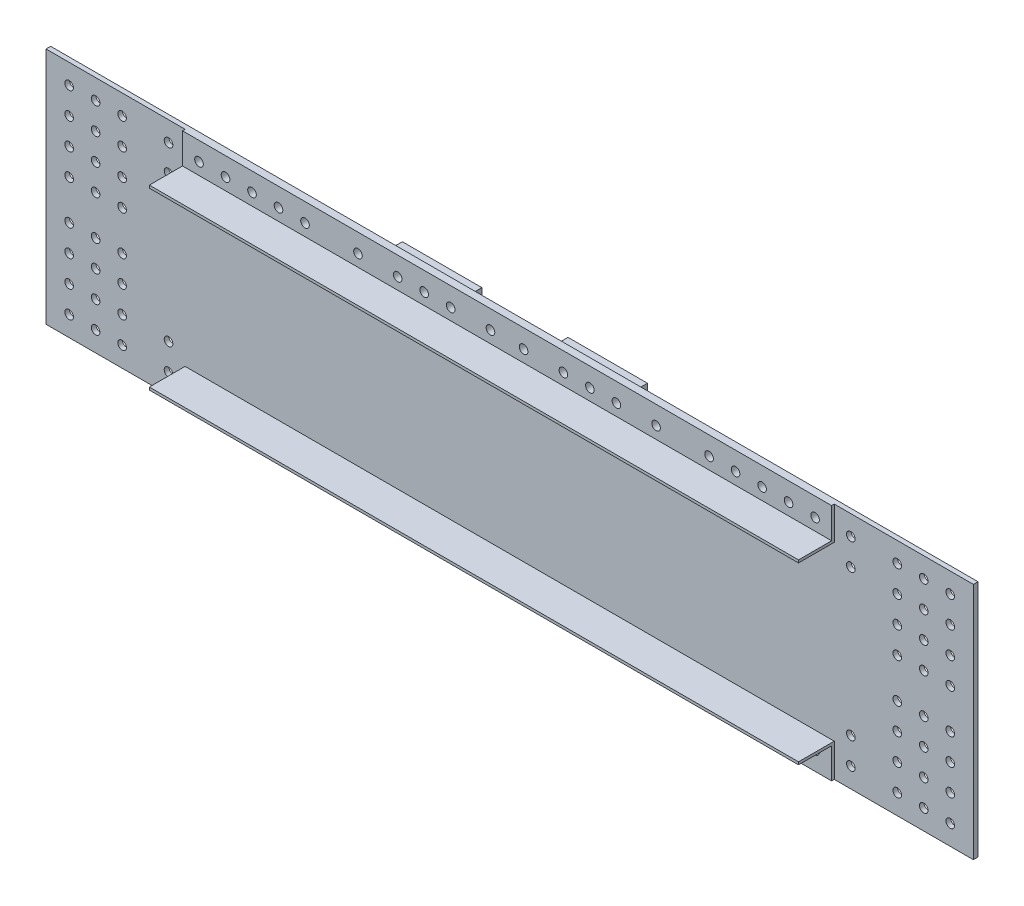
SolidWorks part; units mm, degrees
note: The reader was unsure of these and kept them because the rebuilt part matched: shared geometry of "草图11<3>".
ref_plane "前视基准面" through (0, 0, 0) normal (0, 0, 1) x (1, 0, 0)
ref_plane "上视基准面" through (0, 0, 0) normal (0, 1, 0) x (1, 0, 0)
ref_plane "右视基准面" through (0, 0, 0) normal (1, 0, 0) x (0, 0, -1)
sketch "草图1" plane through (0, 0, 0) normal (0, 0, 1) x (1, 0, 0)
  line L1 (-1400, 360) -> (1400, 360)
  line L2 (-1400, 360) -> (-1400, -360)
  line L3 (-1400, -360) -> (1400, -360)
  line L4 (1400, 360) -> (1400, -360)
  line L5 (-1400, 360) -> (1400, -360) construction
  line L6 (-1400, -360) -> (1400, 360) construction
  point P0 (0, 0)
extrude "凸台-拉伸1" add sketch "草图1" along normal blind 14
sketch "草图2" plane through (0, 0, 14) normal (0, 0, 1) x (1, 0, 0)
  line L0 (-1400, 300) -> (1400, 300)
  line L1 (-1400, 360) -> (-1400, -360) construction
  line L2 (1400, -360) -> (1400, 360) construction
  line L3 (1400, 360) -> (-1400, 360) construction
  line L4 (-1400, 304) -> (1400, 304)
  line L5 (-1330, 360) -> (-1330, -360)
  line L6 (-1400, -360) -> (1400, -360) construction
  line L7 (-1030, 360) -> (-1030, -360)
  line L8 (-980, 360) -> (-980, -360)
  dimension "D1" = 60
  dimension "D2" = 56
  dimension "D3" = 70
  dimension "D4" = 370
  dimension "D5" = 420
sketch "草图3" plane through (0, 0, 14) normal (0, 0, 1) x (1, 0, 0)
  circle A0 centre (-1330.2106, 299.6366) radius 13
extrude "切除-拉伸1" cut sketch "草图3" against normal through all
pattern_linear "阵列(线性)1" count 3 spacing 80 along (1, 0, 0) count 4 spacing 80 along (0, -1, 0) of "切除-拉伸1"
sketch "草图4" plane through (0, 0, 14) normal (0, 0, 1) x (1, 0, 0)
  circle A0 centre (-1030.0292, 300.0161) radius 13
extrude "切除-拉伸2" cut sketch "草图4" against normal through all
pattern_linear "阵列(线性)2" count 2 spacing 80 along (0, -1, 0) of "切除-拉伸2"
mirror "镜向1" about plane through (0, 0, 0) normal (0, 1, 0) of "阵列(线性)1", "阵列(线性)2", "切除-拉伸1", "切除-拉伸2"
mirror "镜向2" about plane through (0, 0, 0) normal (1, 0, 0) of "镜向1", "切除-拉伸1", "阵列(线性)1", "切除-拉伸2", "阵列(线性)2"
sketch "草图5" plane through (0, 0, 14) normal (0, 0, 1) x (1, 0, 0)
  line L1 (-980, 360) -> (0, 360)
  line L2 (-980, 360) -> (-980, 260)
  line L3 (-980, 260) -> (0, 260)
  line L4 (0, 360) -> (0, 260)
extrude "凸台-拉伸2" add sketch "草图5" along normal blind 8
sketch "草图6" plane through (0, 0, 14) normal (0, 0, 1) x (1, 0, 0)
  line L0 (-930, 360) -> (-930, -360)
  line L1 (0, 360) -> (-980, 360) construction
  line L2 (-1400, -360) -> (1400, -360) construction
  line L3 (-980, 360) -> (-980, -360) construction
  line L4 (-450, 360) -> (-450, -360)
  line L5 (-330, 360) -> (-330, -360)
  line L6 (-50, 360) -> (-50, -360)
  dimension "D1" = 50
  dimension "D2" = 530
  dimension "D3" = 650
  dimension "D4" = 930
sketch "草图7" plane through (0, 0, 22) normal (0, 0, 1) x (1, 0, 0)
  line L0 (-1400, 304) -> (1400, 304) construction
  line L1 (-930, 360) -> (-930, -360) construction
  circle A0 centre (-930, 304) radius 13
extrude "切除-拉伸3" cut sketch "草图7" against normal through all
pattern_linear "阵列(线性)3" count 5 spacing 80 along (1, 0, 0) of "切除-拉伸3"
sketch "草图8" plane through (0, 0, 22) normal (0, 0, 1) x (1, 0, 0)
  line L0 (-1400, 304) -> (1400, 304) construction
  line L1 (-450, 360) -> (-450, -360) construction
  line L2 (-50, 360) -> (-50, -360) construction
  circle A0 centre (-450, 304) radius 13
  circle A1 centre (-50, 304) radius 13
extrude "切除-拉伸4" cut sketch "草图8" against normal through all
sketch "草图9" plane through (0, 0, 22) normal (0, 0, 1) x (1, 0, 0)
  line L0 (0, 260) -> (0, 360) construction
  line L1 (-980, 260) -> (0, 260)
  line L2 (-980, 260) -> (-980, 268)
  line L3 (-980, 268) -> (0, 268)
  line L4 (0, 260) -> (0, 268)
extrude "凸台-拉伸3" add sketch "草图9" along normal blind 100
mirror "镜向3" about plane through (0, 0, 0) normal (0, 1, 0) of "凸台-拉伸2", "阵列(线性)3", "切除-拉伸4", "凸台-拉伸3", "切除-拉伸3"
mirror "镜向4" about plane through (0, 0, 0) normal (1, 0, 0) of "镜向3", "凸台-拉伸2", "切除-拉伸3", "阵列(线性)3", "切除-拉伸4"
sketch "草图10" plane through (0, 0, 0) normal (0, 0, -1) x (-1, 0, 0)
  line L0 (370, -360) -> (370, 360)
  line L1 (1400, -360) -> (-1400, -360) construction
  line L2 (-1400, 360) -> (1400, 360) construction
  line L3 (330, 360) -> (330, -360) construction
  dimension "D1" = 40
sketch "草图11" plane through (0, 0, 22) normal (0, 0, 1) x (1, 0, 0)
  line L0 (-370, -360) -> (-370, 360) construction
  line L1 (-370, 268) -> (-130, 268)
  line L2 (-370, 268) -> (-370, 348)
  line L3 (-370, 348) -> (-130, 348)
  line L4 (-130, 268) -> (-130, 348)
  line L5 (980, 268) -> (-980, 268) construction
extrude "凸台-拉伸4" add sketch "草图11" against normal blind 32
sketch "草图12" plane through (0, 0, 22) normal (0, 0, 1) x (1, 0, 0)
  line L0 (-1400, 304) -> (1400, 304) construction
  line L1 (-330, 360) -> (-330, -360) construction
  circle A0 centre (-330, 304) radius 13
extrude "切除-拉伸5" cut sketch "草图12" against normal through all
pattern_linear "阵列(线性)4" count 3 spacing 80 along (1, 0, 0) of "切除-拉伸5"
extrude "凸台-拉伸6" add sketch "草图11<3>" against normal blind 54
sketch "草图11<3>" plane through (0, 0, 22) normal (0, 0, 1) x (1, 0, 0) same geometry as "草图11"
sketch "草图13" plane through (0, 0, 22) normal (0, 0, 1) x (1, 0, 0)
  circle A0 centre (-330.2041, 303.1944) radius 13
extrude "切除-拉伸6" cut sketch "草图13" against normal through all
pattern_linear "阵列(线性)5" count 3 spacing 80 along (1, 0, 0) of "切除-拉伸6"
mirror "镜向7" about plane through (0, 0, 0) normal (0, 1, 0) of "凸台-拉伸6", "阵列(线性)5", "切除-拉伸6"
mirror "镜向8" about plane through (0, 0, 0) normal (1, 0, 0) of "镜向7", "凸台-拉伸6", "切除-拉伸6", "阵列(线性)5"
